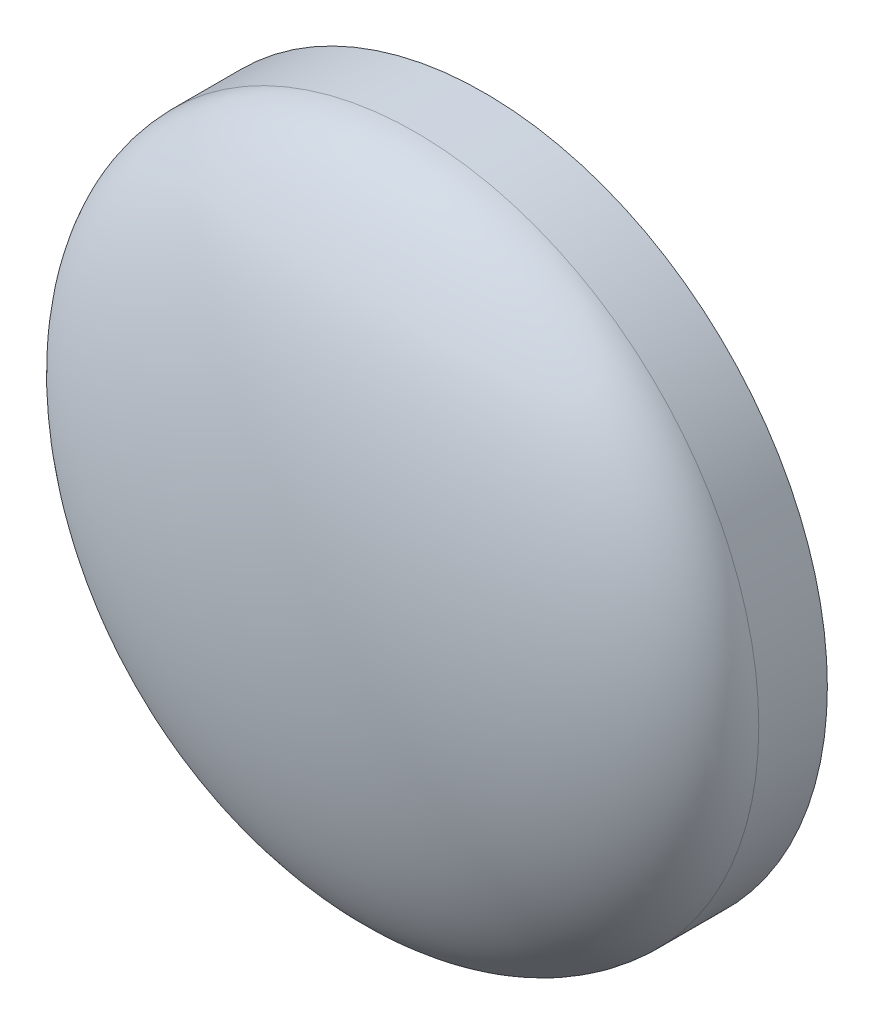
SolidWorks part; units mm, degrees
material "Chêne"
ref_plane "Plan de face" through (0, 0, 0) normal (0, 0, 1) x (1, 0, 0)
ref_plane "Plan de dessus" through (0, 0, 0) normal (0, 1, 0) x (1, 0, 0)
ref_plane "Plan de droite" through (0, 0, 0) normal (1, 0, 0) x (0, 0, -1)
sketch "Esquisse3" plane through (0, 0, 0) normal (0, 0, 1) x (1, 0, 0)
  line L0 (18.5318, -6.6337) -> (15.1808, -5.1078)
  line L1 (17.0873, -9.7824) -> (13.7634, -8.2225)
  circle A0 centre (3.0466, -1.4571) radius 25
  arc A1 (15.0713, -4.8712) -> (13.511, -8.2941) centre (3.0466, -1.4571) ccw
  arc A2 (18.7937, -7.2617) -> (17.7374, -9.5715) centre (3.0466, -1.4571) cw
  arc A3 (18.7937, -7.2617) -> (18.5318, -6.6337) centre (18.3245, -7.0888) ccw
  arc A4 (17.0873, -9.7824) -> (17.7374, -9.5715) centre (17.2997, -9.3298) ccw
  arc A5 (15.1808, -5.1078) -> (15.0713, -4.8712) centre (15.2637, -4.9258) cw
  arc A6 (13.7634, -8.2225) -> (13.511, -8.2941) centre (13.6784, -8.4035) ccw
extrude "Boss.-Extru.5" add sketch "Esquisse3" along normal blind 5 contours A6 L1 A4 A2 A3 L0 A5 A1 | A0 L1 A6 A1 A5 L0 A3 A2 A4 region at (3.433, -1.6335, 0) region at (-21.2463, -1.4571, 0)
extrude "Enlèv. mat.-Extru.2" cut sketch "Esquisse3<4>" along normal blind 3 contours A6 L1 A4 A2 A3 L0 A5 A1 region at (3.433, -1.6335, 0)
sketch "Esquisse3<4>" plane through (0, 0, 0) normal (0, 0, 1) x (1, 0, 0) same geometry as "Esquisse3"
dome "Dôme1" faces to dome 1 distance 10 reverse direction no elliptical dome yes face at (28.0466, -1.4571, 5) parameters "D1"=10
